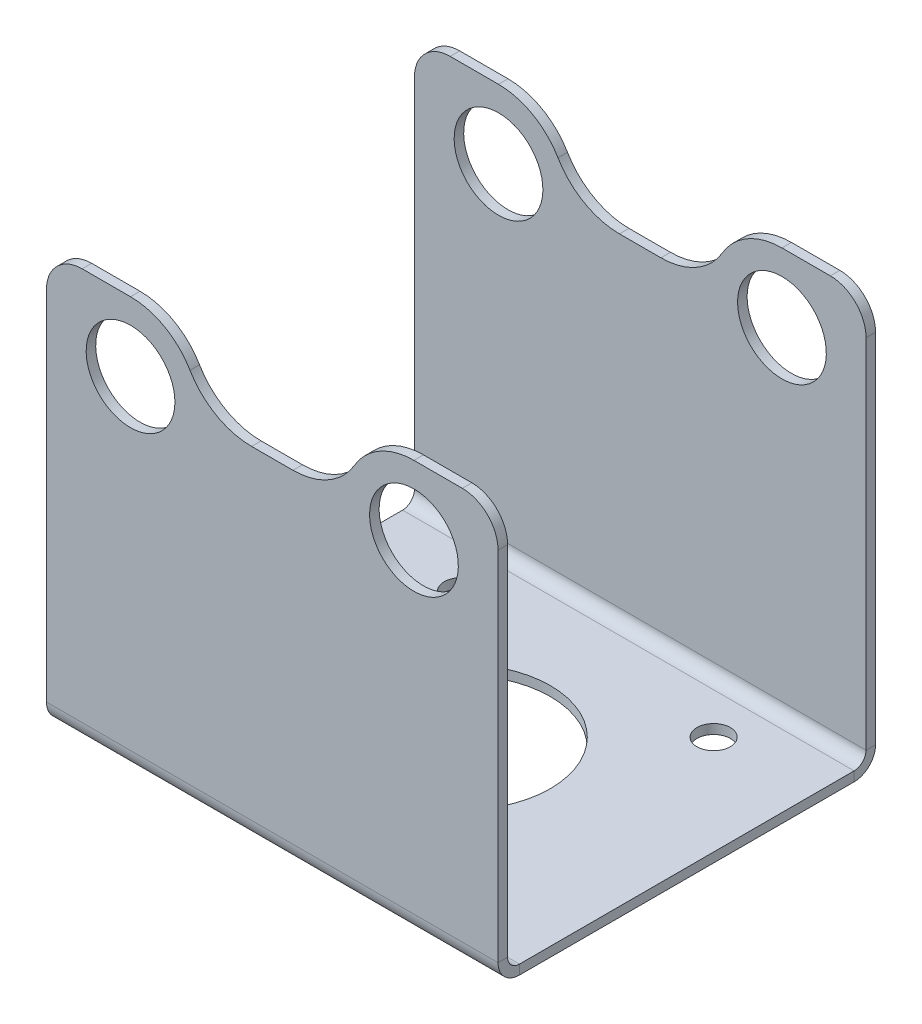
SolidWorks part; units mm, degrees
note: The reader was unsure of these and kept them because the rebuilt part matched: thickness of "Base-Flange1", "Edge-Flange1", "Sheet-Metal1", "Sheet-Metal2", "Sheet-Metal3", "Sheet-Metal11"; flange length of "Edge-Flange1".
material "Brass"
ref_plane "Front Plane" through (0, 0, 0) normal (0, 0, 1) x (1, 0, 0)
ref_plane "Top Plane" through (0, 0, 0) normal (0, 1, 0) x (1, 0, 0)
ref_plane "Right Plane" through (0, 0, 0) normal (1, 0, 0) x (0, 0, -1)
sketch "Sketch1" plane through (0, 0, 0) normal (0, 1, 0) x (1, 0, 0)
  line L0 (-24.0792, 19.1135) -> (24.0792, 19.1135)
  line L1 (24.0792, 19.1135) -> (24.0792, -19.1135)
  line L2 (24.0792, -19.1135) -> (-24.0792, -19.1135)
  line L3 (-24.0792, -19.1135) -> (-24.0792, 19.1135)
  line L4 (-24.0792, -19.1135) -> (24.0792, 19.1135) construction
  line L5 (0, 0) -> (13.4704, 13.4704) construction
  line L6 (0, 0) -> (13.4704, -13.4704) construction
  line L7 (0, 0) -> (0, 19.1135) construction
  line L8 (0, 0) -> (-13.4704, -13.4704) construction
  line L9 (0, 0) -> (-13.4704, 13.4704) construction
  circle A0 centre (0, 0) radius 9.525
  circle A1 centre (13.4704, -13.4704) radius 1.778
  circle A2 centre (13.4704, 13.4704) radius 1.778
  circle A3 centre (-13.4704, 13.4704) radius 1.778
  circle A4 centre (-13.4704, -13.4704) radius 1.778
  point P5 (0, 0)
  dimension "D3" = 19.05
  dimension "D4" = 90
  dimension "D5" = 45
  dimension "D6" = 19.05
  dimension "D8" = 3.556
  dimension "D9" = 3.556
  dimension "D1" = 38.227
  dimension "D2" = 48.1584
  dimension "D7" = 19.05
base flange "Base-Flange1" sketch "Sketch1" thickness 1.016 reverse thickness direction no parameters "D1"=1.27
edge flange "Edge-Flange1" sketch "Sketch10" flange angle 90 flange length 45.7962 flange position material outside bend radius 1.27 thickness 1.016 relief rectangular parameters "D6"=10
sketch "Sketch10" plane through (0, 0, -19.1135) normal (0, 0, -1) x (-1, 0, 0)
  line L0 (-24.0792, 0) -> (24.0792, 0) construction
  line L1 (-24.0792, 0) -> (24.0792, 0)
  line L2 (-24.0792, 0) -> (-24.0792, 44.7802)
  line L3 (-24.0792, 44.7802) -> (24.0792, 44.7802)
  line L4 (24.0792, 44.7802) -> (24.0792, 0)
  line L5 (-24.0792, -1.016) -> (24.0792, -1.016) construction
  line L6 (15.113, 35.814) -> (-15.113, 35.814) construction
  circle A0 centre (-15.113, 35.814) radius 4.7308
  circle A1 centre (15.113, 35.814) radius 4.7308
  dimension "D2" = 8.9662
  dimension "D3" = 9.4615
  dimension "D1" = 36.83
  dimension "D4" = 30.226
  dimension "D5" = 8.9662
  dimension "D6" = 8.9662
  dimension "D7" = 8.9662
bend "EdgeBend1" bend radius 1.27 bend angle 90 parameters "D5"=1
mirror "Mirror1" about plane through (0, 0, 0) normal (0, 0, 1) of "Edge-Flange1"
bend "MirrorBend1" bend radius 1.27 bend angle 90 parameters "D5"=2
sketch "Sketch11" plane through (0, 0, -20.1295) normal (0, 0, -1) x (-1, 0, 0)
  line L2 (24.0792, 44.7802) -> (-24.0792, 44.7802)
  line L5 (7.747, 35.814) -> (-7.747, 35.814)
  line L12 (-15.113, 43.18) -> (-24.0792, 43.18)
  line L13 (-24.0792, 44.7802) -> (-24.0792, 1.27) construction
  line L14 (-24.0792, 43.18) -> (-24.0792, 44.7802)
  line L15 (15.113, 43.18) -> (24.0792, 43.18)
  line L16 (24.0792, 1.27) -> (24.0792, 44.7802) construction
  line L17 (24.0792, 43.18) -> (24.0792, 44.7802)
  circle A2 centre (15.113, 35.814) radius 7.366
  circle A3 centre (-15.113, 35.814) radius 7.366
  dimension "D1" = 14.732
extrude "Cut-Extrude7" cut sketch "Sketch11" against normal through all
fillet "Fillet2" radius 7.62 4 edges at (7.747, 35.814, -19.6215) (-7.747, 35.814, -19.6215) (-7.747, 35.814, 19.6215) (7.747, 35.814, 19.6215)
fillet "Fillet3" radius 3.81 4 edges at (24.0792, 43.18, 19.6215) (-24.0792, 43.18, 19.6215) (-24.0792, 43.18, -19.6215) (24.0792, 43.18, -19.6215)
unfold "Unfold1" [suppressed]
sketch "Sketch11-2" plane through (0, -1.27, -19.7564) normal (0, -1, 0) x (-1, 0, 0)
  line L2 (24.0792, 44.5262) -> (-24.0792, 44.5262)
  line L5 (7.747, 35.56) -> (-7.747, 35.56)
  line L12 (-15.113, 42.926) -> (-24.0792, 42.926)
  line L14 (-24.0792, 42.926) -> (-24.0792, 44.5262)
  line L15 (15.113, 42.926) -> (24.0792, 42.926)
  line L17 (24.0792, 42.926) -> (24.0792, 44.5262)
  circle A2 centre (15.113, 35.56) radius 7.366
  circle A3 centre (-15.113, 35.56) radius 7.366
  dimension "D1" = 14.732
sketch "Bend-Lines1" [suppressed] plane through (0, 0, 0) normal (0, 1, 0) x (1, 0, 0)
sketch "Bounding-Box1" [suppressed] plane through (0, 0, 0) normal (0, 1, 0) x (1, 0, 0)
sheet metal parameters "Sheet-Metal1" thickness 1.016 parameters "D1"=1.27, "D7"=1.27
flat pattern "Flat-Pattern1"
sketch "Bend-Lines2" plane through (0, 0, 0) normal (0, 1, 0) x (1, 0, 0)
sketch3d "Bounding-Box2" [suppressed]
  line L0 (-23.495, 18.034, 0) -> (23.495, 18.034, 0) construction
  line L1 (-23.495, -18.034, 0) -> (23.495, -18.034, 0) construction
  line L2 (-23.495, 18.034, 0) -> (-23.495, -18.034, 0) construction
  line L3 (23.495, 18.034, 0) -> (23.495, -18.034, 0) construction
sheet metal parameters "Sheet-Metal2" thickness 1.016 parameters "D1"=1.27, "D7"=1.27
flat pattern "Flat-Pattern1"
sketch "Bend-Lines2" plane through (0, 0, 0) normal (0, 1, 0) x (1, 0, 0)
  line L0 (23.495, 18.2602) -> (-23.495, 18.2602) construction
  line L1 (23.495, 18.2602) -> (-23.495, 18.2602) construction
sketch3d "Bounding-Box2" [suppressed]
  line L0 (-23.495, -18.034, 0) -> (-23.495, 45.4104, 0) construction
  line L1 (23.495, -18.034, 0) -> (23.495, 45.4104, 0) construction
  line L2 (-23.495, -18.034, 0) -> (23.495, -18.034, 0) construction
  line L3 (-23.495, 45.4104, 0) -> (23.495, 45.4104, 0) construction
bend of the flat pattern "Flatten-<EdgeBend1>1"
sheet metal parameters "Sheet-Metal3" thickness 1.016 parameters "D1"=1.27, "D7"=1.27
flat pattern "Flat-Pattern1" [suppressed]
sketch "Bend-Lines2" plane through (0, 0, 0) normal (0, 1, 0) x (1, 0, 0)
  line L0 (24.0792, 19.5302) -> (-24.0792, 19.5302) construction
  line L1 (24.0792, 19.5302) -> (-24.0792, 19.5302) construction
  line L2 (-24.0792, -19.5302) -> (24.0792, -19.5302) construction
  line L3 (-24.0792, -19.5302) -> (24.0792, -19.5302) construction
sketch3d "Bounding-Box2" [suppressed]
  line L0 (-24.0792, -52.8526, 0) -> (-24.0792, 52.8526, 0) construction
  line L1 (24.0792, -52.8526, 0) -> (24.0792, 52.8526, 0) construction
  line L2 (-24.0792, -52.8526, 0) -> (24.0792, -52.8526, 0) construction
  line L3 (-24.0792, 52.8526, 0) -> (24.0792, 52.8526, 0) construction
bend of the flat pattern "Flatten-<EdgeBend1>1"
bend of the flat pattern "Flatten-<MirrorBend1>1"
sketch "Sketch11-1" plane through (0, -1.27, -19.7564) normal (0, -1, 0) x (-1, 0, 0)
  line L2 (24.0792, 24.13) -> (-24.0792, 24.13)
  line L4 (24.0663, 15.1638) -> (25.4769, 15.1638)
  line L5 (7.747, 15.1638) -> (-7.747, 15.1638)
  line L6 (25.4769, 15.1638) -> (25.4769, 24.13)
  line L7 (25.4769, 24.13) -> (24.0792, 24.13)
  line L8 (-24.0663, 15.1638) -> (-25.6537, 15.1638)
  line L9 (-25.6537, 15.1638) -> (-25.6537, 24.13)
  line L10 (-25.6537, 24.13) -> (-24.0792, 24.13)
  line L12 (24.0792, 1.27) -> (-24.0792, 1.27)
  circle A2 centre (15.113, 15.1638) radius 7.366
  circle A3 centre (-15.113, 15.1638) radius 7.366
  arc A4 (-15.113, 22.5298) -> (-24.0663, 15.1638) centre (-15.9067, 14.3701) ccw
  arc A5 (15.113, 22.5298) -> (24.0663, 15.1638) centre (15.9067, 14.3701) cw
  dimension "D1" = 14.732
  dimension "D3" = 8.1982
  dimension "D2" = 13.1001
sheet metal parameters "Sheet-Metal11" thickness 1.016 parameters "D1"=1.27, "D7"=1.27
flat pattern "Flat-Pattern1"
sketch "Bend-Lines2" plane through (0, 0, -20.1295) normal (0, 0, -1) x (-1, 0, 0)
  line L0 (24.0792, -0.1264) -> (-24.0792, -0.1264) construction
  line L1 (24.0792, -0.1264) -> (-24.0792, -0.1264) construction
  line L2 (24.0792, -38.6063) -> (-24.0792, -38.6063) construction
  line L3 (24.0792, -38.6063) -> (-24.0792, -38.6063) construction
sketch3d "Bounding-Box2" [suppressed]
  line L0 (-24.0793, 43.1799, 0) -> (-24.0792, -81.9128, 0) construction
  line L1 (24.0791, 43.18, 0) -> (24.0792, -81.9127, 0) construction
  line L2 (-24.0793, 43.1799, 0) -> (24.0791, 43.18, 0) construction
  line L3 (-24.0792, -81.9128, 0) -> (24.0792, -81.9127, 0) construction
bend of the flat pattern "Flatten-<MirrorBend1>1"
bend of the flat pattern "Flatten-<EdgeBend1>1"
